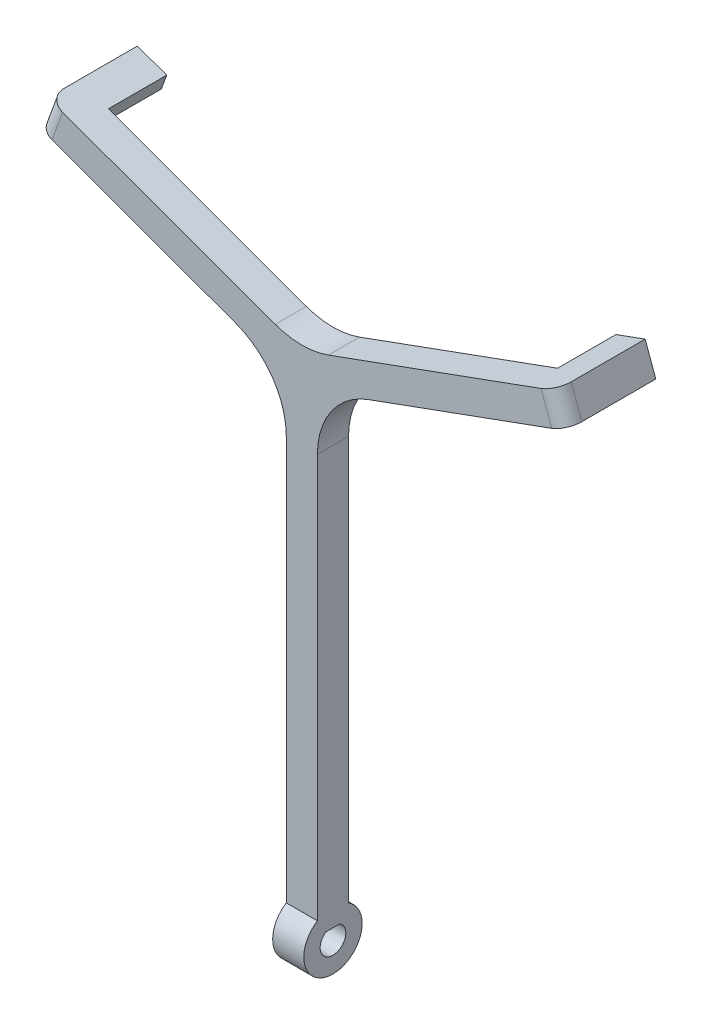
SolidWorks part; units mm, degrees
material "PLA"
ref_plane "Plan de face" through (0, 0, 0) normal (0, 0, 1) x (1, 0, 0)
ref_plane "Plan de dessus" through (0, 0, 0) normal (0, 1, 0) x (1, 0, 0)
ref_plane "Plan de droite" through (0, 0, 0) normal (1, 0, 0) x (0, 0, -1)
sketch "Esquisse1" plane through (0, 0, 0) normal (0, 0, 1) x (1, 0, 0)
  line L1 (0, 0) -> (136, 0) construction
  line L2 (0, 0) -> (0, 155) construction
  line L3 (0, 155) -> (136, 155) construction
  line L4 (136, 0) -> (136, 155) construction
  line L16 (64, 0) -> (64, 124.1884)
  line L17 (64, 124.1884) -> (0, 147.4825)
  line L18 (0, 147.4825) -> (2.7362, 155)
  line L19 (2.7362, 155) -> (68, 131.2459)
  line L20 (68, 131.2459) -> (133.2638, 155)
  line L21 (133.2638, 155) -> (136, 147.4825)
  line L22 (136, 147.4825) -> (72, 124.1884)
  line L23 (72, 124.1884) -> (72, 0)
  line L24 (72, 0) -> (64, 0)
  point P19 (68, 0)
  dimension "D1" = 136
  dimension "D2" = 155
  dimension "D3" = 8
  dimension "D4" = 68
  dimension "D5" = 110
  dimension "D6" = 110
  dimension "D7" = 140
  dimension "D8" = 8
  dimension "D9" = 8
  dimension "D10" = 68
extrude "Boss.-Extru.1" add sketch "Esquisse1" along normal blind 8
sketch "Esquisse2" plane through (0, 0, 0) normal (0, 0, -1) x (-1, 0, 0)
  line L0 (-72, 124.1884) -> (-136, 147.4825) construction
  line L1 (-136, 147.4825) -> (-133.2638, 155) construction
  line L2 (-133.2638, 155) -> (-68, 131.2459) construction
  line L3 (-132.2412, 146.1144) -> (-136, 147.4825)
  line L4 (-136, 147.4825) -> (-133.2638, 155)
  line L5 (-133.2638, 155) -> (-125.7463, 152.2638)
  line L6 (-127.1144, 148.5051) -> (-125.7463, 152.2638)
  line L7 (0, 147.4825) -> (-64, 124.1884) construction
  line L8 (-68, 131.2459) -> (-2.7362, 155) construction
  line L9 (-2.7362, 155) -> (0, 147.4825) construction
  line L10 (0, 147.4825) -> (-3.7588, 146.1144)
  line L11 (-10.2537, 152.2638) -> (-2.7362, 155)
  line L12 (-2.7362, 155) -> (0, 147.4825)
  line L13 (-10.2537, 152.2638) -> (-8.8856, 148.5051)
  line L14 (-132.2412, 146.1144) -> (-127.1144, 148.5051)
  line L15 (-8.8856, 148.5051) -> (-3.7588, 146.1144)
  dimension "D2" = 8
  dimension "D1" = 8
  dimension "D3" = 4
  dimension "D4" = 4
  dimension "D5" = 4
  dimension "D6" = 4
extrude "Boss.-Extru.2" add sketch "Esquisse2" along normal blind 15
fillet "Congé1" radius 20 3 edges at (72, 124.1884, 4) (64, 124.1884, 4) (68, 131.2459, 4)
fillet "Congé2" radius 4 2 edges at (134.6319, 151.2412, 8) (1.3681, 151.2412, 8)
sketch "Esquisse3" plane through (64, 0, 0) normal (-1, 0, 0) x (0, 0, 1)
  line L0 (4, 0) -> (4, 33.6289) construction
  line L1 (8, 0) -> (0, 0) construction
  circle A0 centre (4, 0) radius 7.5
  dimension "D1" = 15
extrude "Boss.-Extru.3" add sketch "Esquisse3" against normal up to surface (8 mm away) up to face at (72, 55.0921, 4)
sketch "Esquisse4" plane through (64, 0, 0) normal (-1, 0, 0) x (0, 0, 1)
  line L7 (4, 0) -> (4, 7.4852) construction
  line L11 (2.2536, 2.8) -> (5.7464, 2.8)
  line L12 (0.3981, -3.3) -> (8.2082, -3.3) construction
  arc A1 (2.2536, 2.8) -> (5.7464, 2.8) centre (4, 0) ccw
  point P10 (4, 6)
  point P11 (4, 6)
  dimension "D1" = 6.6
  dimension "D2" = 6.1
extrude "Enlèv. mat.-Extru.1" cut sketch "Esquisse4" against normal through all
equation "\"long_tot\"=155"
equation "\"espac_sub_arms\"= 120"
equation "\"épaiss_cadre\"=8"
equation "\"long_protub\"= 15"
equation "\"rayon_conge\"= 3"
equation "\"diam_axe\"= 5"
equation "\"D1@Esquisse1\"=\"espac_sub_arms\"+\"épaiss_cadre\"*2"
equation "\"D2@Esquisse1\"=\"long_tot\""
equation "\"D3@Esquisse1\"=\"épaiss_cadre\""
equation "\"D4@Esquisse1\"=\"D1@Esquisse1\"/2"
equation "\"D6@Esquisse1\"=\"D5@Esquisse1\""
equation "\"D8@Esquisse1\"=\"épaiss_cadre\""
equation "\"D9@Esquisse1\"=\"épaiss_cadre\""
equation "\"D10@Esquisse1\"=\"D4@Esquisse1\""
equation "\"D1@Boss.-Extru.1\"=\"épaiss_cadre\""
equation "\"D2@Esquisse2\"=\"épaiss_cadre\""
equation "\"D1@Boss.-Extru.2\"=\"long_protub\""
equation "\"D1@Esquisse2\"=\"épaiss_cadre\""
equation "\"D3@Esquisse2\"=\"D1@Esquisse2\"/2"
equation "\"D4@Esquisse2\"=\"D1@Esquisse2\"/2"
equation "\"D5@Esquisse2\"=\"D2@Esquisse2\"/2"
equation "\"D6@Esquisse2\"=\"D2@Esquisse2\"/2"
